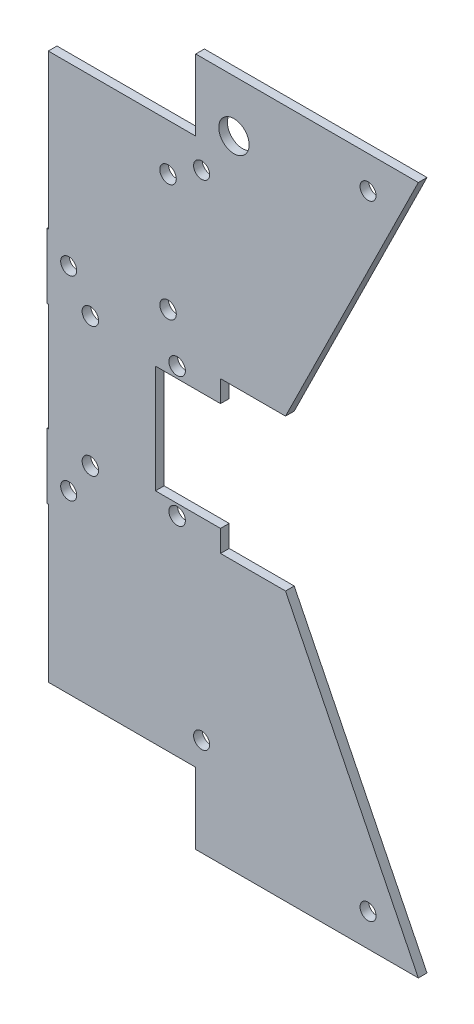
SolidWorks part; units mm, degrees
material "Thornel Mat VMA"
ref_plane "Front Plane" through (0, 0, 0) normal (0, 0, 1) x (1, 0, 0)
ref_plane "Top Plane" through (0, 0, 0) normal (0, 1, 0) x (1, 0, 0)
ref_plane "Right Plane" through (0, 0, 0) normal (1, 0, 0) x (0, 0, -1)
sketch "Sketch1" plane through (0, 0, 0) normal (0, 0, 1) x (1, 0, 0)
  line L0 (-2.9301, -104.5098) -> (-3.3149, -104.5098)
  line L1 (-3.3149, -72.8868) -> (-2.9301, -72.8868)
  line L78 (47.4851, -66.5368) -> (47.4851, -72.8868)
  line L79 (47.4851, -104.5098) -> (47.4851, -110.8598)
  line L80 (66.5174, -66.5368) -> (105.3971, 12.1397)
  line L81 (105.3971, 12.1397) -> (38.7094, 12.1397)
  line L88 (38.7094, 12.1397) -> (38.7094, -8.6883)
  line L89 (-2.9301, -8.6883) -> (38.7094, -8.6883)
  line L90 (-3.3149, -53.8368) -> (-2.9301, -53.8368)
  line L91 (-2.9301, -53.8368) -> (-2.9301, -8.6883)
  line L92 (-3.3149, -66.5368) -> (-3.3149, -53.8368)
  line L93 (-3.3149, -72.8868) -> (-3.3149, -66.5368)
  line L94 (-2.9301, -104.5098) -> (-2.9301, -72.8868)
  line L95 (-3.3149, -110.8598) -> (-3.3149, -104.5098)
  line L96 (66.5174, -110.8598) -> (105.3971, -189.5363)
  line L97 (105.3971, -189.5363) -> (38.7094, -189.5363)
  line L98 (38.7094, -189.5363) -> (38.7094, -168.7083)
  line L99 (-2.9301, -168.7083) -> (38.7094, -168.7083)
  line L106 (-3.3149, -110.8598) -> (-3.3149, -123.5598)
  line L107 (-3.3149, -123.5598) -> (-2.9301, -123.5598)
  line L108 (66.5174, -110.8598) -> (47.4851, -110.8598)
  line L109 (47.4851, -66.5368) -> (66.5174, -66.5368)
  line L110 (47.4851, -104.5098) -> (47.4851, -72.8868)
  line L111 (-2.9301, -123.5598) -> (-2.9301, -168.7083)
  circle A0 centre (90.6739, 2.6147) radius 2.3495
  circle A1 centre (41.9566, -16.4353) radius 2.3495
  circle A2 centre (3.0351, -60.1868) radius 2.3495
  circle A3 centre (3.0351, -117.2098) radius 2.3495
  circle A4 centre (41.9566, -160.9613) radius 2.3495
  circle A5 centre (90.6739, -180.0113) radius 2.3495
  circle A6 centre (51.4094, -3.1003) radius 4.445
  point P2 (90.6739, 2.6147)
  point P4 (41.9566, -16.4353)
  point P6 (3.0351, -60.1868)
  point P8 (3.0351, -117.2098)
  point P10 (41.9566, -160.9613)
  point P11 (90.6739, -180.0113)
  dimension "D2" = 4.699
  dimension "D5" = 8.89
  dimension "D1" = 66.6876
  dimension "D3" = 12.7
  dimension "D4" = 15.24
extrude "Boss-Extrude1" add sketch "Sketch1" along normal blind 2.54
sketch "Sketch2" plane through (0, 0, 2.54) normal (0, 0, 1) x (1, 0, 0)
  line L0 (-3.3149, -53.8368) -> (-3.3149, -72.8868) construction
  line L1 (47.4851, -66.5368) -> (66.5174, -66.5368) construction
  line L2 (47.4851, -88.6983) -> (-2.9301, -88.6983) construction
  line L3 (47.4851, -110.8598) -> (47.4851, -66.5368) construction
  line L4 (-2.9301, -72.8868) -> (-2.9301, -104.5098) construction
  circle A0 centre (9.3851, -69.7118) radius 2.413
  circle A2 centre (34.7851, -69.7118) radius 2.413
  circle A4 centre (34.7851, -107.6848) radius 2.413
  circle A6 centre (9.3851, -107.6848) radius 2.413
  dimension "D1" = 4.826
  dimension "D2" = 25.4
  dimension "D3" = 4.826
  dimension "D5" = 12.7
  dimension "D7" = 3.175
extrude "Cut-Extrude1" cut sketch "Sketch2" against normal through all
sketch "Sketch3" plane through (0, 0, 2.54) normal (0, 0, 1) x (1, 0, 0)
  line L0 (47.4851, -110.8598) -> (47.4851, -66.5368) construction
  line L1 (47.4851, -72.8868) -> (28.4351, -72.8868)
  line L2 (47.4851, -72.8868) -> (47.4851, -104.5098)
  line L3 (47.4851, -104.5098) -> (28.4351, -104.5098)
  line L4 (28.4351, -72.8868) -> (28.4351, -104.5098)
  line L5 (47.4851, -66.5368) -> (66.5174, -66.5368) construction
  line L6 (66.5174, -110.8598) -> (47.4851, -110.8598) construction
  circle A1 centre (9.3851, -69.7118) radius 2.413 construction
  dimension "D3" = 19.05
  dimension "D1" = 6.35
  dimension "D2" = 6.35
extrude "Cut-Extrude2" cut sketch "Sketch3" against normal through all
sketch "Sketch4" plane through (0, 0, 2.54) normal (0, 0, 1) x (1, 0, 0)
  line L0 (-2.9301, -168.7083) -> (38.7094, -168.7083) construction
  line L1 (27.4577, 15.7469) -> (40.2334, 15.7469)
  line L2 (27.4577, 15.7469) -> (27.4577, -8.6883)
  line L3 (27.4577, -8.6883) -> (40.2334, -8.6883)
  line L4 (40.2334, 15.7469) -> (40.2334, -8.6883)
  line L5 (0, -197.042) -> (40.2334, -197.042)
  line L6 (0, -197.042) -> (0, -168.7083)
  line L7 (0, -168.7083) -> (40.2334, -168.7083)
  line L8 (40.2334, -197.042) -> (40.2334, -168.7083)
  line L9 (38.7094, -168.7083) -> (38.7094, -189.5363) construction
  line L10 (38.7094, -8.6883) -> (-2.9301, -8.6883) construction
  dimension "D1" = 1.524
extrude "Cut-Extrude3" cut sketch "Sketch4" against normal through all
sketch "Sketch5" plane through (0, 0, 0) normal (0, 0, -1) x (-1, 0, 0)
  line L0 (2.9301, -8.6883) -> (2.9301, -53.8368) construction
  line L1 (-40.2334, -8.6883) -> (2.9301, -8.6883) construction
  circle A0 centre (-32.1219, -22.4043) radius 2.413
  circle A1 centre (-32.1219, -56.6943) radius 2.413
  dimension "D4" = 4.826
  dimension "D1" = 35.052
  dimension "D2" = 13.716
  dimension "D3" = 34.29
extrude "Cut-Extrude4" cut sketch "Sketch5" against normal through all
